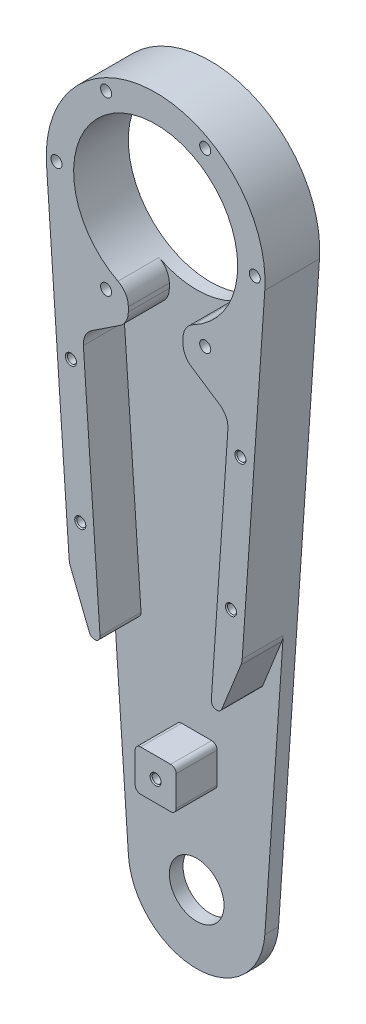
SolidWorks part; units mm, degrees
ref_plane "Front Plane" through (0, 0, 0) normal (0, 0, 1) x (1, 0, 0)
ref_plane "Top Plane" through (0, 0, 0) normal (0, 1, 0) x (1, 0, 0)
ref_plane "Right Plane" through (0, 0, 0) normal (1, 0, 0) x (0, 0, -1)
sketch "Sketch1" plane through (0, 0, 0) normal (0, 0, 1) x (1, 0, 0)
  line L0 (-1000, 0) -> (49000, 0) construction
  line L1 (0, -1000) -> (0, 49000) construction
  circle A0 centre (0, 0) radius 40
  circle A1 centre (0, 0) radius 30
  circle A2 centre (0, 0) radius 36.25 construction
  point P4 (0, 36.25)
  dimension "D1" = 80
  dimension "D2" = 60
  dimension "D3" = 72.5
extrude "Boss-Extrude1" add sketch "Sketch1" against normal blind 5
hole_wizard "M4x0.7 Tapped Hole1" positions "Sketch7" profile "Sketch8" tap size "M4x0.7" standard "ANSI Metric" end condition through all
sketch "Sketch7" plane through (0, 0, 0) normal (0, 0, 1) x (1, 0, 0)
  line L0 (0, 0) -> (36.25, 0) construction
  circle A0 centre (0, 0) radius 36.25 construction
  point P9 (36.25, 0)
cosmetic thread "Hole Thread1" parameters "D2"=4
sketch "Sketch8" plane through (36.25, 0, 0) normal (1, 0, 0) x (0, -1, 0)
  line L0 (0, 0) -> (0, 5)
  line L1 (0, 5) -> (1.65, 5)
  line L2 (1.65, 5) -> (1.65, 0.375)
  line L3 (1.65, 0.375) -> (2.025, 0)
  line L5 (2.025, 0) -> (0, 0)
  line L6 (-1.65, 0.375) -> (-2.025, 0) construction
  line L11 (0, -6.35) -> (0, 107.95) construction
  dimension "Thru Tap Drill Dia." = 3.3
  dimension "Thru Tap Drill Depth" = 5
  dimension "Near C'Sink Dia." = 4.05
  dimension "Near C'Sink Angle" = 90
sketch "Sketch9" plane through (0, 0, 0) normal (1, 0, 0) x (0, 0, -1)
  line L0 (-1000, 0) -> (49000, 0) construction
pattern_circular "CirPattern1" count 6 over 360 about axis through (0, 0, 0) along (0, 0, 1) of "M4x0.7 Tapped Hole1"
cosmetic thread "Hole Thread2" parameters "D2"=4
cosmetic thread "Hole Thread3" parameters "D2"=4
cosmetic thread "Hole Thread4" parameters "D2"=4
cosmetic thread "Hole Thread5" parameters "D2"=4
cosmetic thread "Hole Thread6" parameters "D2"=4
cosmetic thread "Hole Thread7" parameters "D2"=4
cosmetic thread "Hole Thread8" parameters "D2"=4
cosmetic thread "Hole Thread9" parameters "D2"=4
cosmetic thread "Hole Thread10" parameters "D2"=4
cosmetic thread "Hole Thread11" parameters "D2"=4
cosmetic thread "Hole Thread12" parameters "D2"=4
sketch "Sketch14" plane through (0, 0, 0) normal (0, 0, 1) x (1, 0, 0)
  line L0 (-1000, 0) -> (49000, 0) construction
  line L1 (0, -1000) -> (0, 49000) construction
  line L2 (-1000, -220) -> (49000, -220) construction
  line L3 (-39.9069, -2.7273) -> (-24.9418, -221.7045)
  line L4 (39.9069, -2.7273) -> (24.9418, -221.7045)
  circle A0 centre (0, -220) radius 25
  circle A1 centre (0, 0) radius 40 construction
  circle A2 centre (0, 0) radius 40
  circle A3 centre (0, -220) radius 10
  dimension "D2" = 50
  dimension "D3" = 20
  dimension "D1" = 220
extrude "Boss-Extrude5" add sketch "Sketch14" against normal blind 5 contours A2 L3 A0 L4 | A0
sketch "Sketch15" plane through (0, 0, 0) normal (0, 0, 1) x (1, 0, 0)
  line L0 (0, -1000) -> (0, 49000) construction
  line L1 (10, -28.2843) -> (10, -38.2843)
  line L2 (-39.9069, -2.7273) -> (-24.9418, -221.7045)
  line L3 (24.9418, -221.7045) -> (39.9069, -2.7273)
  line L4 (-39.9069, -2.7273) -> (-24.9418, -221.7045)
  line L5 (24.9418, -221.7045) -> (39.9069, -2.7273)
  line L6 (10, -38.2843) -> (10, -28.2843)
  line L7 (10, -38.2843) -> (26.7017, -49.2867)
  line L8 (26.7017, -49.2867) -> (19.4771, -155)
  line L9 (7.5, -185) -> (19.4771, -155)
  line L10 (7.5, -170) -> (-7.5, -170)
  line L11 (19.4771, -155) -> (31.5706, -124.7086)
  line L12 (-26.7017, -49.2867) -> (-19.4771, -155)
  line L13 (-10, -38.2843) -> (-26.7017, -49.2867)
  line L14 (-10, -28.2843) -> (-10, -38.2843)
  line L15 (-19.4771, -155) -> (-31.5706, -124.7086)
  line L16 (-7.5, -185) -> (-19.4771, -155)
  line L17 (-7.5, -170) -> (7.5, -170)
  line L18 (-7.5, -170) -> (-7.5, -185)
  line L19 (7.5, -170) -> (7.5, -185)
  line L20 (-7.5, -185) -> (7.5, -185)
  circle A1 centre (0, 0) radius 30 construction
  arc A2 (39.9069, -2.7273) -> (-39.9069, -2.7273) centre (0, 0) ccw
  arc A3 (-24.9418, -221.7045) -> (24.9418, -221.7045) centre (0, -220) ccw
  arc A4 (39.9069, -2.7273) -> (-39.9069, -2.7273) centre (0, 0) ccw
  arc A5 (-24.9418, -221.7045) -> (24.9418, -221.7045) centre (0, -220) ccw
  circle A6 centre (0, 0) radius 30
  point P17 (0, -177.5)
  point P22 (0, -170)
  dimension "D2" = 50
  dimension "D3" = 10
  dimension "D4" = 10
  dimension "D5" = 10
  dimension "D6" = 30
  dimension "D7" = 20
  dimension "D8" = 7.5
  dimension "D9" = 15
  dimension "D10" = 7.5
  dimension "D1" = 0
extrude "Boss-Extrude7" add sketch "Sketch15" along normal blind 15
sketch "Sketch21" plane through (0, 0, 15) normal (0, 0, 1) x (1, 0, 0)
  line L0 (-1000, -60) -> (49000, -60) construction
  line L1 (-34.9186, -2.3864) -> (-19.9535, -221.3636) construction
  line L2 (-1000, -110) -> (49000, -110) construction
  line L3 (19.9535, -221.3636) -> (34.9186, -2.3864) construction
  line L6 (24.9418, -221.7045) -> (39.9069, -2.7273) construction
  line L7 (-39.9069, -2.7273) -> (-24.9418, -221.7045) construction
  line L8 (24.9418, -221.7045) -> (39.9069, -2.7273) construction
  line L9 (-39.9069, -2.7273) -> (-24.9418, -221.7045) construction
  point P0 (0, -177.5)
  point P5 (0, 0)
  point P8 (0, 0)
  point P17 (-30.9812, -60)
  point P18 (-27.5641, -110)
  point P21 (27.5641, -110)
  point P22 (30.9812, -60)
  dimension "D1" = 50
  dimension "D3" = 60
  dimension "D4" = 5
hole_wizard "M4x0.7 Tapped Hole2" positions "Sketch22" profile "Sketch23" tap size "M4x0.7" standard "ANSI Metric"
sketch "Sketch22" plane through (0, 0, 15) normal (0, 0, 1) x (1, 0, 0)
  point P0 (0, -177.5)
  point P10 (-27.5641, -110)
  point P13 (27.5641, -110)
  point P16 (-30.9812, -60)
  point P19 (30.9812, -60)
  point P23 (0, 0)
  point P24 (0, 0)
cosmetic thread "Hole Thread13" parameters "D1"=15, "D2"=4
cosmetic thread "Hole Thread14" parameters "D1"=15, "D2"=4
cosmetic thread "Hole Thread15" parameters "D1"=15, "D2"=4
cosmetic thread "Hole Thread16" parameters "D1"=15, "D2"=4
cosmetic thread "Hole Thread17" parameters "D1"=15, "D2"=4
sketch "Sketch23" plane through (0, -177.5, 15) normal (1, 0, 0) x (0, -1, 0)
  line L0 (0, 0) -> (0, 15.9914)
  line L1 (0, 15.9914) -> (1.65, 15)
  line L2 (1.65, 15) -> (1.65, 0.375)
  line L3 (1.65, 0.375) -> (2.025, 0)
  line L5 (2.025, 0) -> (0, 0)
  line L6 (-1.65, 0.375) -> (-2.025, 0) construction
  line L10 (0, 15.9914) -> (-1.65, 15) construction
  line L11 (0, -6.35) -> (0, 107.95) construction
  dimension "Tap Drill Dia." = 3.3
  dimension "Tap Drill Depth" = 15
  dimension "Near C'Sink Dia." = 4.05
  dimension "Near C'Sink Angle" = 90
  dimension "Drill Angle" = 118
fillet "Fillet1" radius 7 8 edges at (31.5706, -124.7086, 7.5) (26.7017, -49.2867, 7.5) (10, -38.2843, 7.5) (10, -28.2843, 7.5) (-31.5706, -124.7086, 7.5) (-26.7017, -49.2867, 7.5) (-10, -38.2843, 7.5) (-10, -28.2843, 7.5)
fillet "Fillet2" radius 2 6 edges at (-7.5, -170, 7.5) (-7.5, -185, 7.5) (7.5, -185, 7.5) (7.5, -170, 7.5) (19.4771, -155, 7.5) (-19.4771, -155, 7.5)
